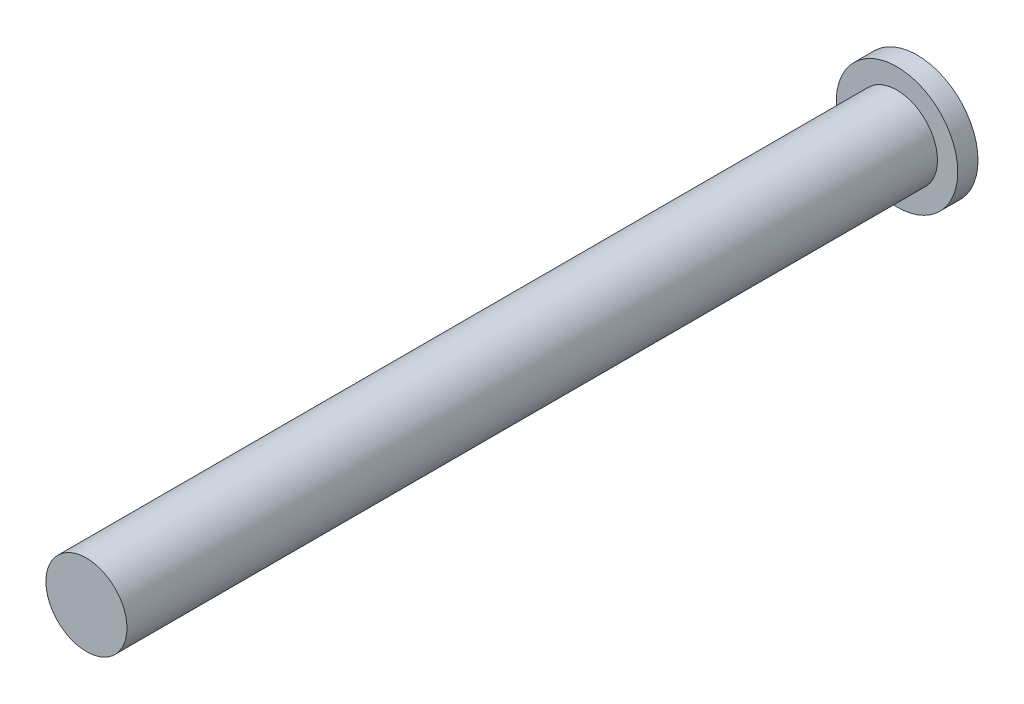
SolidWorks part; units mm, degrees
ref_plane "Plan de face" through (0, 0, 0) normal (0, 0, 1) x (1, 0, 0)
ref_plane "Plan de dessus" through (0, 0, 0) normal (0, 1, 0) x (1, 0, 0)
ref_plane "Plan de droite" through (0, 0, 0) normal (1, 0, 0) x (0, 0, -1)
sketch "Esquisse1" plane through (0, 0, 0) normal (0, 0, 1) x (1, 0, 0)
  circle A0 centre (0, 0) radius 3
  circle A1 centre (0, 0) radius 2
  dimension "D1" = 4
  dimension "D2" = 6
extrude "Boss.-Extru.1" add sketch "Esquisse1" along normal blind 40 contours A1 region at (0, 0, 0)
extrude "Boss.-Extru.2" add sketch "Esquisse1<3>" against normal blind 1 contours A0 A1 | A1 region at (-2.9151, 0, 0) region at (0, 0, 0)
sketch "Esquisse1<3>" plane through (0, 0, 0) normal (0, 0, 1) x (1, 0, 0) same geometry as "Esquisse1"
